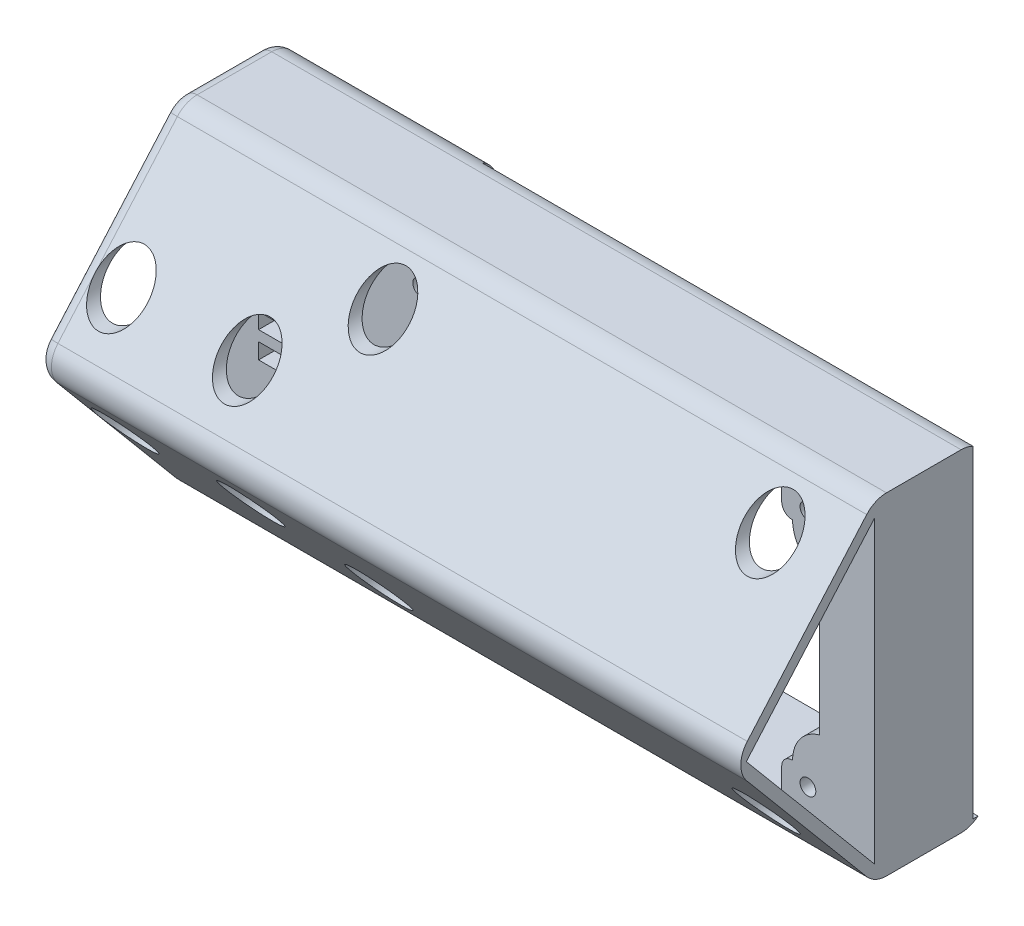
SolidWorks part; units mm, degrees
note: The reader was unsure of these and kept them because the rebuilt part matched: shared geometry of "Sketch30<3>".
ref_plane "Front Plane" through (0, 0, 0) normal (0, 0, 1) x (1, 0, 0)
ref_plane "Top Plane" through (0, 0, 0) normal (0, 1, 0) x (1, 0, 0)
ref_plane "Right Plane" through (0, 0, 0) normal (1, 0, 0) x (0, 0, -1)
sketch "SideScreenView" plane through (0, 0, 0) normal (1, 0, 0) x (0, 0, -1)
  line L0 (0, 0) -> (0, 63.28)
  line L1 (0, 63.28) -> (21.5, 63.28)
  line L2 (21.5, 63.28) -> (21.5, 0)
  line L3 (21.5, 0) -> (0, 0)
  line L4 (0, 63.28) -> (-27.0861, 32.28)
  line L6 (18.75, 59.86) -> (15, 59.86)
  line L7 (15, 59.86) -> (15, 4.7)
  line L8 (15, 4.7) -> (18.75, 4.7)
  line L9 (18.75, 4.7) -> (18.75, 59.86)
  line L10 (11, 56.56) -> (15, 56.56)
  line L11 (15, 56.56) -> (15, 53.56)
  line L12 (15, 53.56) -> (11, 53.56)
  line L13 (11, 55.06) -> (11, 59.86) construction
  line L14 (11, 11) -> (15, 11)
  line L15 (15, 11) -> (15, 8)
  line L16 (15, 8) -> (11, 8)
  line L17 (11, 9.5) -> (11, 4.7) construction
  line L18 (11, 11) -> (11, 8)
  line L19 (11, 56.56) -> (11, 53.56)
  line L20 (15, 59.86) -> (11, 59.86) construction
  line L21 (18.75, 62.78) -> (21.5, 62.78)
  line L22 (21.5, 62.78) -> (21.5, 1.78)
  line L23 (21.5, 1.78) -> (18.75, 1.78)
  line L24 (18.75, 1.78) -> (18.75, 62.78)
  line L25 (11, 4.7) -> (15, 4.7) construction
  line L27 (-27.0861, 32.28) -> (0, 0)
  line L28 (1.5061, 61.9641) -> (-24.4532, 32.2537)
  line L29 (-24.4532, 32.2537) -> (1.5321, 1.2856)
  line L30 (11, 56.56) -> (0, 56.56) construction
  line L31 (11, 53.56) -> (0, 53.56) construction
  line L32 (11, 11) -> (0, 11) construction
  line L33 (11, 8) -> (0, 8) construction
  line L34 (0, 36.28) -> (4, 36.28)
  line L35 (0, 36.28) -> (0, 28.28)
  line L36 (4, 36.28) -> (4, 28.28)
  line L37 (0, 28.28) -> (4, 28.28)
  line L38 (0, 32.28) -> (15, 32.28) construction
  line L39 (4, 28.28) -> (4, 11) construction
  line L40 (4, 21.78) -> (9, 21.78)
  line L41 (4, 21.78) -> (4, 42.78)
  line L42 (9, 21.78) -> (9, 42.78)
  line L43 (4, 42.78) -> (9, 42.78)
  line L44 (4, 21.78) -> (9, 42.78) construction
  line L45 (9, 21.78) -> (4, 42.78) construction
  line L46 (4, 36.28) -> (9, 36.28)
  line L47 (9, 36.28) -> (9, 28.28)
  line L48 (9, 28.28) -> (4, 28.28)
  line L49 (9, 42.78) -> (9, 53.56) construction
  line L52 (0, 0) -> (21.5, 0)
  point P26 (18.75, 32.28)
  point P28 (18.75, 32.28)
  point P39 (6.5, 32.28)
  dimension "D3" = 55.16
  dimension "D4" = 3
  dimension "D5" = 4.8
  dimension "D6" = 4
  dimension "D7" = 61
  dimension "D8" = 6.5
  dimension "D9" = 8
  dimension "ThisArbitrary" = 2.75
  dimension "D10" = 4
  dimension "D11" = 40
  dimension "D12" = 8
  dimension "D13" = 2
  dimension "D14" = 2
  dimension "D16" = 0.5
  dimension "D19" = 21
  dimension "D20" = 15.3379
  dimension "D21" = 5
sketch "SideButtonView" plane through (0, 0, 0) normal (1, 0, 0) x (0, 0, -1)
  line L0 (21.5, 0) -> (0, 0) construction
  line L1 (0, 0) -> (0, 63.28) construction
  line L2 (0, 63.28) -> (21.5, 63.28) construction
  line L3 (21.5, 63.28) -> (21.5, 0) construction
  line L4 (21.5, 0) -> (0, 0)
  line L5 (0, 0) -> (0, 63.28)
  line L6 (0, 63.28) -> (21.5, 63.28)
  line L7 (21.5, 63.28) -> (21.5, 0)
  line L8 (15.7, 48.89) -> (30.7, 48.89)
  line L9 (30.7, 48.89) -> (30.7, 14.39)
  line L10 (30.7, 14.39) -> (15.7, 14.39)
  line L11 (15.7, 14.39) -> (15.7, 48.89)
  line L12 (15.7, 30.14) -> (15.7, 33.14)
  line L13 (15.7, 30.14) -> (11.2, 30.14)
  line L14 (15.7, 33.14) -> (11.2, 33.14)
  line L15 (11.2, 30.14) -> (11.2, 33.14)
  line L16 (11.2, 33.14) -> (30.7, 33.14) construction
  line L17 (11.2, 30.14) -> (11.2, 33.14)
  line L18 (11.2, 30.14) -> (9.5, 30.14)
  line L19 (11.2, 33.14) -> (9.5, 33.14)
  line L20 (9.5, 30.14) -> (9.5, 33.14)
  line L21 (6, 48.14) -> (9.5, 48.14)
  line L22 (6, 48.14) -> (6, 15.14)
  line L23 (9.5, 48.14) -> (9.5, 15.14)
  line L24 (6, 15.14) -> (9.5, 15.14)
  line L25 (6, 21.14) -> (6, 18.14)
  line L26 (6, 21.14) -> (2.5, 21.14)
  line L27 (6, 18.14) -> (2.5, 18.14)
  line L28 (2.5, 21.14) -> (2.5, 18.14)
  line L29 (6, 42.14) -> (6, 45.14)
  line L30 (6, 42.14) -> (2.5, 42.14)
  line L31 (6, 45.14) -> (2.5, 45.14)
  line L32 (2.5, 42.14) -> (2.5, 45.14)
  line L33 (2.5, 18.14) -> (9.5, 18.14) construction
  line L34 (2.5, 43.64) -> (2.5, 19.64) construction
  line L35 (6, 31.64) -> (2.5, 31.64) construction
  line L36 (2.5, 31.64) -> (0, 31.64) construction
  point P6 (9.5, 31.64)
  point P11 (15.7, 31.64)
  point P12 (9.5, 31.64)
  point P14 (15.7, 31.64)
  point P18 (11.2, 31.64)
  point P22 (11.2, 31.64)
  point P38 (2.5, 31.64)
  dimension "D1" = 34.5
  dimension "D2" = 15
  dimension "D3" = 19.5
  dimension "D4" = 7
  dimension "D5" = 8.7
  dimension "D6" = 24
  dimension "D7" = 3
  dimension "D8" = 2.5
  dimension "D9" = 3
  dimension "D10" = 3.5
  dimension "D11" = 33
sketch "Sketch3" plane through (0, 0, 0) normal (0, 1, 0) x (1, 0, 0)
  line L0 (-2, 21.5) -> (0, 21.5)
  dimension "D1" = 2
ref_plane "Plane1" through (0, 0, -21.5) normal (0, 0, 1) x (1, 0, 0)
sketch "FrontView" plane through (0, 0, -21.5) normal (0, 0, 1) x (1, 0, 0)
  line L0 (0, 63.28) -> (0, 0)
  line L1 (0, 63.28) -> (-133.94, 63.28)
  line L2 (0, 0) -> (-133.94, 0)
  line L3 (-133.94, 63.28) -> (-133.94, 0)
  line L4 (-0.5, 62.78) -> (-92.94, 62.78)
  line L5 (-0.5, 62.78) -> (-0.5, 1.78)
  line L6 (-92.94, 62.78) -> (-92.94, 1.78)
  line L7 (-0.5, 1.78) -> (-92.94, 1.78)
  line L8 (-15.882, 51.878) -> (-15.882, 12.682)
  line L9 (-7.9, 59.86) -> (-91.34, 59.86)
  line L10 (-7.9, 59.86) -> (-7.9, 4.7)
  line L11 (-7.9, 4.7) -> (-91.34, 4.7)
  line L12 (-91.34, 59.86) -> (-91.34, 4.7)
  line L17 (-15.882, 12.682) -> (-83.358, 12.682)
  line L18 (-83.358, 51.878) -> (-83.358, 12.682)
  line L19 (-15.882, 51.878) -> (-83.358, 51.878)
  line L20 (-97.94, 15.14) -> (-130.94, 48.14) construction
  line L21 (-97.94, 48.14) -> (-130.94, 48.14)
  line L22 (-97.94, 48.14) -> (-97.94, 15.14)
  line L23 (-97.94, 15.14) -> (-130.94, 15.14)
  line L24 (-130.94, 48.14) -> (-130.94, 15.14)
  line L25 (-126.44, 19.64) -> (-102.44, 43.64) construction
  line L26 (-133.94, 41.64) -> (-130.94, 41.64) construction
  line L27 (-133.94, 21.64) -> (-130.94, 21.64) construction
  line L28 (-133.94, 41.64) -> (-133.94, 21.64) construction
  line L49 (-86.12, 42.78) -> (-13.12, 42.78) construction
  line L50 (-86.12, 42.78) -> (-86.12, 21.78) construction
  line L51 (-13.12, 42.78) -> (-13.12, 21.78) construction
  line L52 (-86.12, 21.78) -> (-13.12, 21.78) construction
  line L53 (-49.62, 12.682) -> (-49.62, 21.78) construction
  line L54 (-13.12, 27.81) -> (0, 27.81)
  line L55 (-13.12, 27.81) -> (-13.12, 36.75)
  line L56 (-13.12, 36.75) -> (0, 36.75)
  line L57 (0, 27.81) -> (0, 36.75)
  line L58 (-88.12, 44.78) -> (-11.12, 44.78)
  line L59 (-11.12, 44.78) -> (-11.12, 19.78)
  line L60 (-88.12, 19.78) -> (-11.12, 19.78)
  line L61 (-88.12, 44.78) -> (-88.12, 19.78)
  line L62 (-97.94, 41.64) -> (-91.34, 41.64)
  line L63 (-97.94, 21.64) -> (-91.34, 21.64)
  line L70 (-117.44, 27.64) -> (-117.44, 35.64)
  line L71 (-117.44, 27.64) -> (-111.44, 27.64)
  line L72 (-117.44, 35.64) -> (-111.44, 35.64)
  line L73 (-111.44, 27.64) -> (-111.44, 35.64)
  line L74 (-117.44, 27.64) -> (-111.44, 35.64) construction
  line L75 (-117.44, 35.64) -> (-111.44, 27.64) construction
  line L76 (-117.44, 32.64) -> (-111.44, 32.64)
  line L77 (-117.44, 30.64) -> (-111.44, 30.64)
  line L78 (-114.44, 32.64) -> (-114.44, 30.64) construction
  circle A0 centre (-86.54, 55.06) radius 2.25
  circle A2 centre (-114.44, 31.64) radius 17.25 construction
  point P15 (-86.54, 55.06)
  point P18 (-12.7, 55.06)
  point P19 (-86.54, 9.5)
  point P20 (-12.7, 9.5)
  point P34 (-126.44, 43.64)
  point P35 (-102.44, 19.64)
  point P36 (-126.44, 19.64)
  point P37 (-102.44, 43.64)
  point P40 (-114.44, 31.64)
  point P41 (-114.44, 31.64)
  point P42 (-133.94, 31.64)
  point P45 (-13.12, 32.28)
  point P52 (-13.12, 32.28)
  point P94 (-114.44, 31.64)
  dimension "D8" = 4.5
  dimension "D9" = 2.25
  dimension "D13" = 34.5
  dimension "D1" = 92.44
  dimension "D2" = 4.8
  dimension "D3" = 4.8
  dimension "D4" = 4.8
  dimension "D5" = 4.8
  dimension "D6" = 1.6
  dimension "D7" = 83.44
  dimension "D10" = 0.5
  dimension "D11" = 24
  dimension "D12" = 24
  dimension "D14" = 5
  dimension "D15" = 73
  dimension "D16" = 20
  dimension "D17" = 3
  dimension "D18" = 21
  dimension "D19" = 6.03
  dimension "D20" = 2
  dimension "D22" = 8
  dimension "D23" = 6
  dimension "D24" = 2
sketch "Sketch5" plane through (0, 0, 0) normal (1, 0, 0) x (0, 0, -1)
  line L0 (21.5, 63.28) -> (21.5, 0) construction
  line L1 (21.5, 0) -> (0, 0) construction
  line L2 (0, 0) -> (0, 63.28) construction
  line L3 (0, 63.28) -> (21.5, 63.28) construction
  line L4 (21.5, 63.28) -> (21.5, 0)
  line L5 (21.5, 0) -> (0, 0)
  line L6 (0, 0) -> (0, 63.28)
  line L7 (0, 63.28) -> (21.5, 63.28)
  line L17 (0, 0) -> (21.5, 0) construction
  line L18 (0, 0) -> (21.5, 0)
extrude "Boss-Extrude1" add sketch "Sketch5" against normal up to vertex (133.94 mm away) up to point (-133.94, 63.28, -21.5)
hole_wizard "Ø3.0mm Dowel Hole4" positions "Sketch6" profile "Sketch7" hole size "Ø3.0" standard "ANSI Metric" end condition through all
sketch "Sketch6" plane through (0, 0, -21.5) normal (0, 0, -1) x (-1, 0, 0)
  point P0 (12.7, 55.06)
  point P3 (86.54, 55.06)
  point P6 (86.54, 9.5)
  point P9 (12.7, 9.5)
sketch "Sketch7" plane through (-12.7, 55.06, -21.5) normal (1, 0, 0) x (0, 1, 0)
  line L0 (0, 0) -> (0, 21.5)
  line L1 (0, 21.5) -> (1.5, 21.5)
  line L2 (1.5, 21.5) -> (1.5, 0.025)
  line L3 (1.5, 0.025) -> (1.525, 0)
  line L5 (1.525, 0) -> (0, 0)
  line L6 (-1.5, 0.025) -> (-1.525, 0) construction
  line L11 (0, -6.35) -> (0, 107.95) construction
  dimension "Thru Hole Dia." = 3
  dimension "Thru Hole Depth" = 21.5
  dimension "Near C'Sink Dia." = 3.05
  dimension "Near C'Sink Angle" = 90
sketch "Sketch8" plane through (0, 0, -21.5) normal (0, 0, 1) x (1, 0, 0)
  line L0 (-83.358, 51.878) -> (-83.358, 12.682) construction
  line L1 (-15.882, 12.682) -> (-83.358, 12.682) construction
  line L2 (-15.882, 51.878) -> (-15.882, 12.682) construction
  line L3 (-15.882, 51.878) -> (-83.358, 51.878) construction
  line L4 (-83.358, 51.878) -> (-83.358, 12.682) construction
  line L5 (-15.882, 12.682) -> (-83.358, 12.682) construction
  line L6 (-15.882, 51.878) -> (-15.882, 12.682) construction
  line L7 (-15.882, 51.878) -> (-83.358, 51.878) construction
  line L8 (-15.632, 52.128) -> (-83.608, 52.128)
  line L9 (-83.608, 52.128) -> (-83.608, 12.432)
  line L10 (-15.632, 12.432) -> (-83.608, 12.432)
  line L11 (-15.632, 52.128) -> (-15.632, 12.432)
  dimension "D1" = 0.25
extrude "Cut-Extrude1" cut sketch "Sketch8" along normal through all
sketch "Sketch9" plane through (0, 0, -21.5) normal (0, 0, 1) x (1, 0, 0)
  line L0 (-7.9, 59.86) -> (-7.9, 4.7) construction
  line L1 (-7.9, 4.7) -> (-91.34, 4.7) construction
  line L2 (-91.34, 59.86) -> (-91.34, 4.7) construction
  line L3 (-7.9, 59.86) -> (-91.34, 59.86) construction
  line L4 (-7.9, 59.86) -> (-7.9, 4.7) construction
  line L5 (-7.9, 4.7) -> (-91.34, 4.7) construction
  line L6 (-91.34, 59.86) -> (-91.34, 4.7) construction
  line L7 (-7.9, 59.86) -> (-91.34, 59.86) construction
  line L8 (-7.3, 60.46) -> (-7.3, 4.1)
  line L9 (-7.3, 4.1) -> (-91.94, 4.1)
  line L10 (-91.94, 60.46) -> (-91.94, 4.1)
  line L11 (-7.3, 60.46) -> (-91.94, 60.46)
  dimension "D1" = 0.6
extrude "Cut-Extrude2" cut sketch "Sketch9" along normal up to vertex (6.5 mm away) up to point (0, 59.86, -15)
sketch "Sketch10" plane through (0, 0, -21.5) normal (0, 0, 1) x (1, 0, 0)
  line L0 (-0.5, 62.78) -> (-92.94, 62.78) construction
  line L1 (-92.94, 62.78) -> (-92.94, 1.78) construction
  line L2 (-0.5, 1.78) -> (-92.94, 1.78) construction
  line L3 (-0.5, 62.78) -> (-0.5, 1.78) construction
  line L4 (-0.5, 62.78) -> (-92.94, 62.78) construction
  line L5 (-92.94, 62.78) -> (-92.94, 1.78) construction
  line L6 (-0.5, 1.78) -> (-92.94, 1.78) construction
  line L7 (-0.5, 62.78) -> (-0.5, 1.78) construction
  line L8 (0.1, 63.38) -> (-93.54, 63.38)
  line L9 (-93.54, 63.38) -> (-93.54, 1.18)
  line L10 (0.1, 1.18) -> (-93.54, 1.18)
  line L11 (0.1, 63.38) -> (0.1, 1.18)
  dimension "D1" = 0.6
extrude "Cut-Extrude3" cut sketch "Sketch10" along normal up to vertex (2.75 mm away) up to point (0, 62.78, -18.75)
sketch "Sketch13" plane through (0, 0, -21.5) normal (0, 0, -1) x (-1, 0, 0)
  line L0 (97.94, 15.14) -> (130.94, 15.14) construction
  line L1 (130.94, 48.14) -> (130.94, 15.14) construction
  line L2 (97.94, 48.14) -> (97.94, 15.14) construction
  line L3 (97.94, 48.14) -> (130.94, 48.14) construction
  line L4 (83.608, 15.14) -> (130.94, 15.14) construction
  line L5 (130.94, 48.14) -> (130.94, 15.14) construction
  line L6 (97.94, 48.14) -> (97.94, 41.64) construction
  line L7 (97.94, 48.14) -> (130.94, 48.14) construction
  line L8 (133.94, 63.28) -> (133.94, 0) construction
  line L9 (83.608, 52.128) -> (83.608, 12.432) construction
  line L10 (97.34, 41.89) -> (83.608, 41.89)
  line L11 (133.94, 63.28) -> (133.94, 0)
  line L12 (83.608, 14.54) -> (83.608, 41.89)
  line L13 (97.94, 41.64) -> (91.34, 41.64) construction
  line L14 (97.94, 41.89) -> (83.608, 41.89) construction
  line L15 (97.34, 42.24) -> (97.34, 41.89)
  line L16 (97.94, 41.64) -> (83.608, 41.64) construction
  line L23 (83.608, 14.54) -> (131.54, 14.54)
  line L24 (131.54, 48.74) -> (131.54, 14.54)
  line L25 (97.34, 48.74) -> (131.54, 48.74)
  line L26 (97.34, 48.74) -> (97.34, 42.24)
  line L32 (70.8408, 14.54) -> (81.2183, 18.2876) construction
  line L33 (74.2687, 15.14) -> (81.7869, 17.855) construction
  line L34 (70.8408, 14.54) -> (83.608, 14.54) construction
  line L35 (74.2687, 15.14) -> (83.608, 15.14) construction
  line L36 (97.34, 42.24) -> (83.0522, 42.24) construction
  line L37 (83.608, 41.64) -> (81.7869, 17.855) construction
  line L38 (83.0522, 42.24) -> (81.2183, 18.2876) construction
  dimension "D1" = 0.6
  dimension "D2" = 0.25
extrude "Cut-Extrude4" cut sketch "Sketch13" against normal up to vertex (15.5 mm away)
sketch "Sketch38" plane through (0, 0, -15) normal (0, 0, -1) x (-1, 0, 0)
  circle A0 centre (12.7, 55.06) radius 4
  circle A1 centre (86.54, 55.06) radius 4
  circle A2 centre (86.54, 9.5) radius 4
  circle A3 centre (12.7, 9.5) radius 4
  dimension "D1" = 8
extrude "Cut-Extrude13" cut sketch "Sketch38" against normal blind 4
sketch "Sketch23" plane through (0, 0, -21.5) normal (0, 0, -1) x (1, 0, 0)
  line L0 (-11.12, -44.78) -> (-11.12, -19.78) construction
  line L1 (-88.12, -44.78) -> (-11.12, -44.78) construction
  line L2 (-88.12, -44.78) -> (-88.12, -19.78) construction
  line L3 (-88.12, -19.78) -> (-11.12, -19.78) construction
  line L4 (-11.12, -44.78) -> (-11.12, -19.78) construction
  line L5 (-88.12, -44.78) -> (-11.12, -44.78) construction
  line L6 (-88.12, -44.78) -> (-88.12, -19.78) construction
  line L7 (-88.12, -19.78) -> (-11.12, -19.78) construction
  line L8 (-10.52, -45.38) -> (-10.52, -19.18)
  line L9 (-88.72, -19.18) -> (-10.52, -19.18)
  line L10 (-88.72, -45.38) -> (-88.72, -19.18)
  line L11 (-88.72, -45.38) -> (-10.52, -45.38)
  dimension "D1" = 0.6
extrude "Cut-Extrude5" cut sketch "Sketch23" along normal through all from surface at -21.5 starting at face at (-66.97, 31.64, 0)
sketch "Sketch39" plane through (0, 0, -15) normal (0, 0, -1) x (-1, 0, 0)
  line L0 (91.94, 60.46) -> (7.3, 60.46) construction
  line L1 (17.7, 60.46) -> (81.54, 60.46)
  line L2 (17.7, 60.46) -> (17.7, 4.1)
  line L3 (17.7, 4.1) -> (81.54, 4.1)
  line L4 (81.54, 60.46) -> (81.54, 4.1)
  line L5 (7.3, 4.1) -> (91.94, 4.1) construction
  circle A0 centre (86.54, 9.5) radius 4 construction
  circle A1 centre (86.54, 55.06) radius 4 construction
  circle A2 centre (12.7, 9.5) radius 4 construction
  circle A3 centre (12.7, 55.06) radius 4 construction
  circle A8 centre (86.54, 9.5) radius 4
  circle A9 centre (86.54, 55.06) radius 4
  circle A10 centre (12.7, 9.5) radius 4
  circle A11 centre (12.7, 55.06) radius 4
  circle A12 centre (12.7, 55.06) radius 5
  circle A13 centre (86.54, 55.06) radius 5
  circle A14 centre (12.7, 9.5) radius 5
  circle A15 centre (86.54, 9.5) radius 5
  line M14 (15.632, 52.128) -> (83.608, 52.128)
  line M20 (91.94, 60.46) -> (7.3, 60.46)
  line M22 (7.3, 4.1) -> (91.94, 4.1)
  line M26 (83.608, 12.432) -> (15.632, 12.432)
  dimension "D1" = 1
extrude "Cut-Extrude15" cut sketch "Sketch39" against normal through all contours L4 L2 M20 M14 | L4 L2 M26 M22 | L4 L2 M14 M26
sketch "Sketch30" plane through (0, 0, -21.5) normal (0, 0, -1) x (1, 0, 0)
  line L0 (-117.44, -35.64) -> (-111.44, -35.64) construction
  line L1 (-111.44, -27.64) -> (-111.44, -35.64) construction
  line L2 (-117.44, -27.64) -> (-111.44, -27.64) construction
  line L3 (-117.44, -27.64) -> (-117.44, -35.64) construction
  line L4 (-117.44, -35.64) -> (-111.44, -35.64)
  line L5 (-111.44, -27.64) -> (-111.44, -35.64)
  line L6 (-117.44, -27.64) -> (-111.44, -27.64)
  line L7 (-117.44, -27.64) -> (-117.44, -35.64)
  line L8 (-117.44, -32.64) -> (-111.44, -32.64) construction
  line L9 (-117.44, -30.64) -> (-111.44, -30.64) construction
  line L10 (-117.44, -32.64) -> (-111.44, -32.64)
  line L11 (-117.44, -30.64) -> (-111.44, -30.64)
extrude "Cut-Extrude7" cut sketch "Sketch30" against normal through all contours L10 L7 L4 L5 | L7 L11 L5 L6
extrude "Boss-Extrude4" add sketch "Sketch30<3>" along normal blind 3.5 from surface at -15.5 separate body contours L11 L7 L10 L5 starting at face at (-114.44, 29.14, -6)
sketch "Sketch30<3>" plane through (0, 0, -21.5) normal (0, 0, -1) x (1, 0, 0) same geometry as "Sketch30"
sketch "Sketch31" plane through (0, 0, 0) normal (1, 0, 0) x (0, 0, -1)
  line L0 (0, 63.28) -> (-27.0861, 32.28) construction
  line L1 (-27.0861, 32.28) -> (0, 0) construction
  line L2 (-24.4532, 32.2537) -> (1.5321, 1.2856) construction
  line L3 (1.5061, 61.9641) -> (-24.4532, 32.2537) construction
  line L4 (0, 63.28) -> (-27.0861, 32.28)
  line L5 (-27.0861, 32.28) -> (0, 0)
  line L6 (-24.4532, 32.2537) -> (1.5321, 1.2856)
  line L7 (1.5061, 61.9641) -> (-24.4532, 32.2537)
  line L8 (0, 0) -> (0, 63.28) construction
  line L9 (0, 0) -> (0, 63.28)
extrude "Boss-Extrude3" add sketch "Sketch31" against normal up to vertex (133.94 mm away) contours L5 L9 L6 L7 L4 up to point (-133.94, 0, 0)
sketch "Sketch32" plane through (0, 0, -6) normal (0, 0, -1) x (-1, 0, 0)
  circle A0 centre (102.44, 43.64) radius 1.8
  circle A1 centre (126.44, 43.64) radius 1.8
  circle A2 centre (102.44, 19.64) radius 1.8
  circle A3 centre (126.44, 19.64) radius 1.8
  dimension "D1" = 3.6
extrude "Cut-Extrude8" cut sketch "Sketch32" against normal up to surface (6 mm away) up to face at (-12.7, 56.56, 0)
fillet "Fillet1" radius 5 5 edges at (-66.97, 32.28, 27.0861) (-66.97, 0, 0) (-66.97, 0, -21.5) (-66.97, 63.28, 0) (-113.74, 63.28, -21.5)
fillet "Fillet5" radius 2.5 1 edges at (-133.94, 31.6759, 0)
fillet "Fillet8" radius 2.5 10 edges at (-133.94, 62.8324, -0.2033) (-133.94, 61.8155, -20.0355) (-133.94, 1.4645, -20.0355) (-133.94, 0.4685, -0.2184) (-133.94, 63.28, -9.3855) (-133.94, 31.64, -21.5) (-133.94, 0, -9.4158) (-133.94, 15.3932, 12.9164) (-133.94, 48.537, 12.8817) (-133.94, 32.2642, 25.5037)
fillet "Fillet15" radius 7 4 edges at (-83.608, 45.38, -7.5) (-15.632, 45.38, -7.5) (-15.632, 19.18, -7.5) (-83.608, 19.18, -3)
fillet "Fillet16" radius 0.5 4 edges at (-114.44, 30.64, -9.5) (-114.44, 32.64, -9.5) (-117.44, 31.64, -9.5) (-111.44, 31.64, -9.5)
fillet "Fillet17" radius 2 2 edges at (-97.34, 48.74, -13.75) (-97.34, 41.89, -13.75)
fillet "Fillet18" radius 2 4 edges at (-81.54, 12.432, -7.5) (-17.7, 12.432, -7.5) (-17.7, 52.128, -7.5) (-81.54, 52.128, -7.5)
hole_wizard "Ø10.0 (10) Diameter Hole1" positions "Sketch40" profile "Sketch41" hole size "Ø10.0" standard "ANSI Metric" end condition through all
sketch "Sketch40" plane through (0, 0, 0) normal (0, 0, 1) x (1, 0, 0)
  point P0 (-86.54, 55.06)
  point P3 (-12.7, 55.06)
  point P6 (-12.7, 9.5)
  point P9 (-86.54, 9.5)
  point P12 (-102.44, 43.64)
  point P15 (-126.44, 43.64)
  point P18 (-126.44, 19.64)
  point P21 (-102.44, 19.64)
sketch "Sketch41" plane through (-86.54, 55.06, 0) normal (1, 0, 0) x (0, 1, 0)
  line L0 (0, 0) -> (0, 25.5039)
  line L1 (0, 25.5039) -> (5, 25.5039)
  line L2 (5, 25.5039) -> (5, 0)
  line L5 (5, 0) -> (0, 0)
  line L11 (0, -6.35) -> (0, 107.95) construction
  dimension "Thru Hole Dia." = 10
  dimension "Thru Hole Depth" = 25.5039
